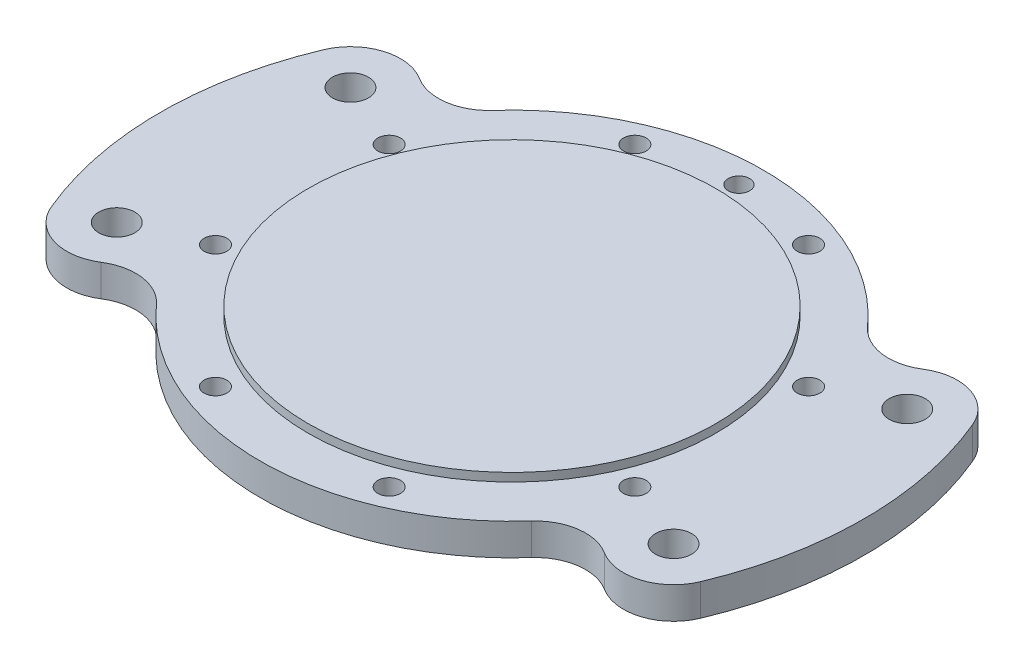
SolidWorks part; units mm, degrees
ref_plane "Front Plane" through (0, 0, 0) normal (0, 0, 1) x (1, 0, 0)
ref_plane "Top Plane" through (0, 0, 0) normal (0, 1, 0) x (1, 0, 0)
ref_plane "Right Plane" through (0, 0, 0) normal (1, 0, 0) x (0, 0, -1)
sketch "Sketch1" plane through (0, 0, 0) normal (0, 1, 0) x (1, 0, 0)
  line L0 (0, 42.5788) -> (0, -44.3324) construction
  line L1 (-13.0112, 31.4119) -> (0, 0) construction
  line L2 (41.7019, 17.5) -> (41.7019, -17.5) construction
  line L3 (31.8836, 20.1646) -> (44.561, 28.1823)
  line L4 (-64.518, 0) -> (71.4295, 0) construction
  line L5 (0, 0) -> (44.561, 28.1823) construction
  line L6 (31.8836, -20.1646) -> (44.561, -28.1823)
  line L7 (-31.8836, -20.1646) -> (-44.561, -28.1823)
  line L8 (-31.8836, 20.1646) -> (-44.561, 28.1823)
  circle A0 centre (0, 0) radius 37.725 construction
  circle A1 centre (-13.0112, 31.4119) radius 1
  circle A2 centre (13.0112, 31.4119) radius 1
  circle A3 centre (31.4119, 13.0112) radius 1
  circle A4 centre (31.4119, -13.0112) radius 1
  circle A5 centre (13.0112, -31.4119) radius 1
  circle A6 centre (-13.0112, -31.4119) radius 1
  circle A7 centre (-31.4119, -13.0112) radius 1
  circle A8 centre (-31.4119, 13.0112) radius 1
  circle A9 centre (41.7019, 17.5) radius 2.7
  circle A10 centre (41.7019, -17.5) radius 2.7
  circle A11 centre (0, 0) radius 52.725 construction
  arc A12 (44.561, 28.1823) -> (44.561, -28.1823) centre (0, 0) cw
  arc A13 (-31.8836, 20.1646) -> (31.8836, 20.1646) centre (0, 0) cw
  arc A14 (-31.8836, -20.1646) -> (31.8836, -20.1646) centre (0, 0) ccw
  circle A15 centre (-41.7019, 17.5) radius 2.7
  circle A16 centre (-41.7019, -17.5) radius 2.7
  arc A17 (-44.561, 28.1823) -> (-44.561, -28.1823) centre (0, 0) ccw
  point P23 (0, 0)
  point P27 (41.7019, 0)
  dimension "D1" = 75.45
  dimension "D3" = 2
  dimension "D6" = 15
  dimension "D9" = 5.4
  dimension "D2" = 34
  dimension "D4" = 22.5
  dimension "D7" = 45.225
  dimension "D8" = 35
  dimension "D10" = 7.5
  dimension "D5" = 8
extrude "Boss-Extrude1" add sketch "Sketch1" along normal blind 6
fillet "Fillet1" radius 7.5 8 edges at (44.561, 3, 28.1823) (31.8836, 3, 20.1646) (-44.561, 3, 28.1823) (-31.8836, 3, 20.1646) (44.561, 3, -28.1823) (31.8836, 3, -20.1646) (-44.561, 3, -28.1823) (-31.8836, 3, -20.1646)
sketch "Sketch2" plane through (0, 6, 0) normal (0, 1, 0) x (1, 0, 0)
  circle A0 centre (0, 34) radius 1.6
  dimension "D2" = 3.2
  dimension "D1" = 34
extrude "Cut-Extrude1" cut sketch "Sketch2" against normal through all
sketch "Sketch3" plane through (0, 6, 0) normal (0, 1, 0) x (1, 0, 0)
  arc A0 (28.0981, 25.1728) -> (-28.0981, 25.1728) centre (0, 0) ccw construction
  circle A1 centre (0, 0) radius 30.525
  dimension "D1" = 7.2
extrude "Cut-Extrude3" cut sketch "Sketch3" against normal blind 1.25 flip side to cut
hole_wizard "CSK for M3 Flat Head Machine Screw1" positions "Sketch9" profile "Sketch8" countersink size "M3" standard "ANSI Metric" end condition through all
sketch "Sketch9" plane through (0, 0, 0) normal (0, -1, 0) x (-1, 0, 0)
  point P0 (13.0112, -31.4119)
  point P3 (-13.0112, -31.4119)
  point P6 (-31.4119, -13.0112)
  point P9 (-31.4119, 13.0112)
  point P12 (-13.0112, 31.4119)
  point P15 (13.0112, 31.4119)
  point P18 (31.4119, 13.0112)
  point P21 (31.4119, -13.0112)
sketch "Sketch8" plane through (-13.0112, 0, 31.4119) normal (1, 0, 0) x (0, 0, -1)
  line L0 (0, 0) -> (0, 6)
  line L1 (0, 6) -> (1.7, 6)
  line L2 (1.7, 6) -> (1.7, 1.45)
  line L3 (1.7, 1.45) -> (3.15, 0)
  line L5 (3.15, 0) -> (0, 0)
  line L6 (-1.7, 1.45) -> (-3.15, 0) construction
  line L11 (0, -6.35) -> (0, 107.95) construction
  dimension "Thru Hole Dia." = 3.4
  dimension "Thru Hole Depth" = 6
  dimension "Near C'Sink Dia." = 6.3
  dimension "Near C'Sink Angle" = 90
equation "\"D7@Sketch1\"=\"D1@Sketch1\"/2+\"D6@Sketch1\"/2"
